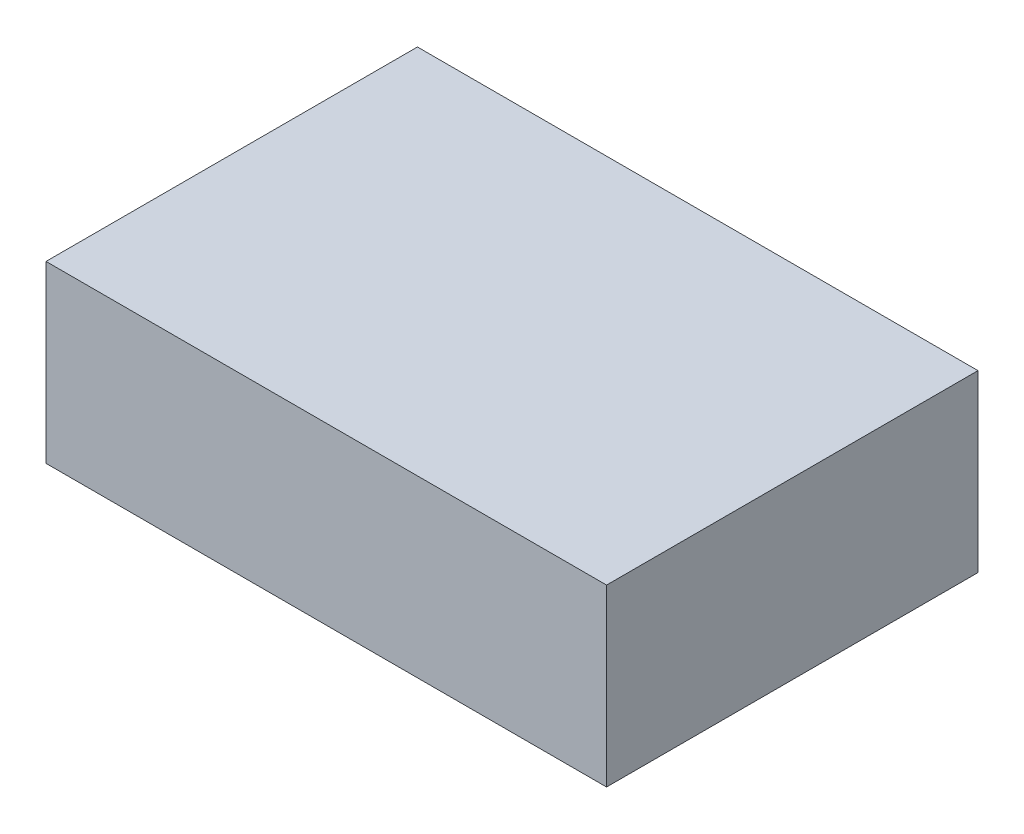
SolidWorks part; units mm, degrees
ref_plane "Front Plane" through (0, 0, 0) normal (0, 0, 1) x (1, 0, 0)
ref_plane "Top Plane" through (0, 0, 0) normal (0, 1, 0) x (1, 0, 0)
ref_plane "Right Plane" through (0, 0, 0) normal (1, 0, 0) x (0, 0, -1)
sketch "Sketch1" plane through (0, 38.1, 0) normal (0, 1, 0) x (1, 0, 0)
  line L1 (-160.2422, -1156.1779) -> (160.2422, -1156.1779)
  line L2 (-160.2422, -1156.1779) -> (-160.2422, -943.8221)
  line L3 (-160.2422, -943.8221) -> (160.2422, -943.8221)
  line L4 (160.2422, -1156.1779) -> (160.2422, -943.8221)
  line L5 (-160.2422, -1156.1779) -> (160.2422, -943.8221) construction
  line L6 (-160.2422, -943.8221) -> (160.2422, -1156.1779) construction
  point P0 (0, -1050)
extrude "Boss-Extrude1" add sketch "Sketch1" along normal blind 100
